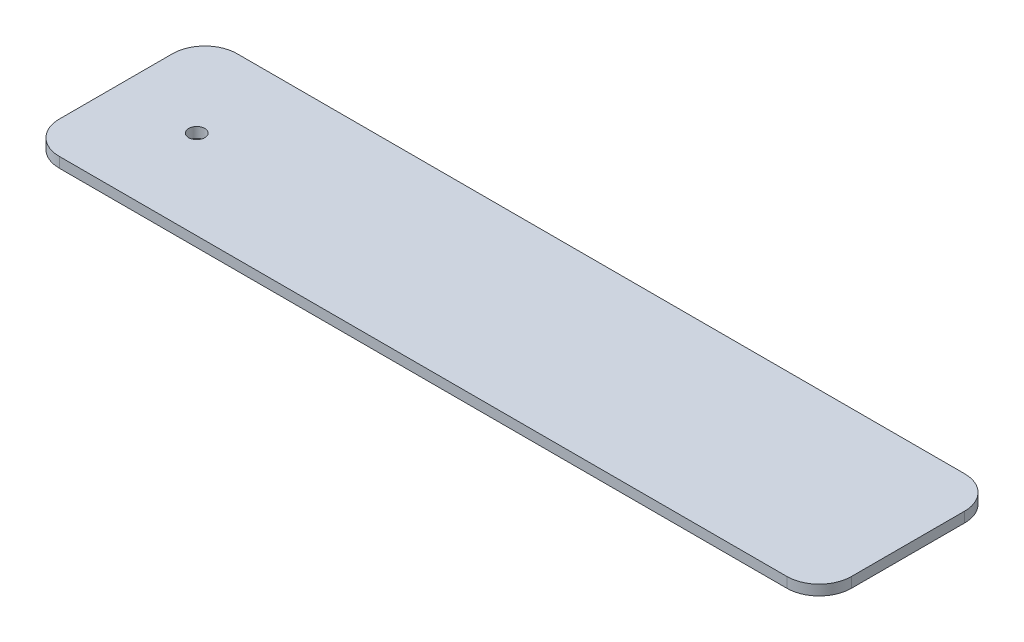
SolidWorks part; units mm, degrees
ref_plane "Front Plane" through (0, 0, 0) normal (0, 0, 1) x (1, 0, 0)
ref_plane "Top Plane" through (0, 0, 0) normal (0, 1, 0) x (1, 0, 0)
ref_plane "Right Plane" through (0, 0, 0) normal (1, 0, 0) x (0, 0, -1)
sketch "Sketch1" plane through (0, 0, 0) normal (0, 1, 0) x (1, 0, 0)
  line L0 (-25, 0) -> (0, 0) construction
  line L1 (-25, 27.5) -> (220, 27.5)
  line L2 (-25, 27.5) -> (-25, -27.5)
  line L3 (-25, -27.5) -> (220, -27.5)
  line L4 (220, 27.5) -> (220, -27.5)
  point P7 (200, 0)
  point P8 (0, 0)
  dimension "D1" = 55
  dimension "D2" = 200
  dimension "D3" = 20
  dimension "D4" = 25
extrude "Boss-Extrude1" add sketch "Sketch1" along normal blind 3.175
fillet "Fillet1" radius 10 4 edges at (-25, 1.5875, 27.5) (-25, 1.5875, -27.5) (220, 1.5875, -27.5) (220, 1.5875, 27.5)
hole_wizard "Ø5.0mm Dowel Hole1" positions "Sketch3" profile "Sketch4" hole size "Ø5.0" standard "DIN" end condition up to next
sketch "Sketch3" plane through (0, 3.175, 0) normal (0, 1, 0) x (1, 0, 0)
  point P0 (0, 0)
sketch "Sketch4" plane through (0, 3.175, 0) normal (1, 0, 0) x (0, 0, 1)
  line L0 (0, 0) -> (0, 3.175)
  line L1 (0, 3.175) -> (2.5, 3.175)
  line L2 (2.5, 3.175) -> (2.5, 0)
  line L5 (2.5, 0) -> (0, 0)
  line L11 (0, -6.35) -> (0, 107.95) construction
  dimension "Thru Hole Dia." = 5
  dimension "Thru Hole Depth" = 3.175
equation "\"Pivot to Pivot Distance\"= 200mm"
equation "\"D2@Sketch1\"=\"Pivot to Pivot Distance\""
equation "\"Plate Thickness\"= 0.125in"
equation "\"D1@Boss-Extrude1\"=\"Plate Thickness\""
